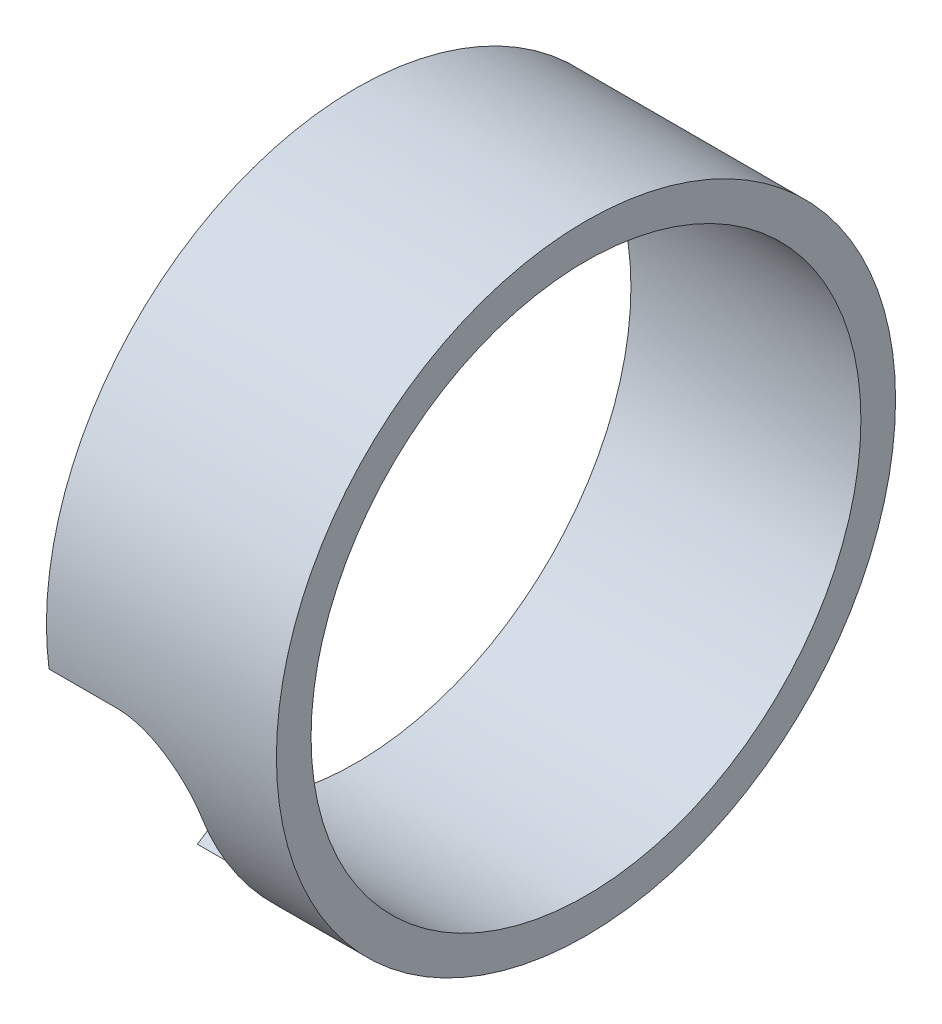
SolidWorks part; units mm, degrees
material "Nylon 6/10"
ref_plane "Front Plane" through (0, 0, 0) normal (0, 0, 1) x (1, 0, 0)
ref_plane "Top Plane" through (0, 0, 0) normal (0, 1, 0) x (1, 0, 0)
ref_plane "Right Plane" through (0, 0, 0) normal (1, 0, 0) x (0, 0, -1)
sketch "Sketch1" plane through (0, 0, 0) normal (0, 0, 1) x (1, 0, 0)
  line L0 (-25.4, 7.5) -> (-42.315, 7.5) construction
  line L1 (-39.013, 8.7312) -> (-32.527, 8.7312)
  line L2 (-39.013, 8.7312) -> (-39.013, 7.754)
  line L3 (-39.013, 7.754) -> (-32.527, 7.754)
  line L4 (-32.527, 8.7312) -> (-32.527, 7.754)
  line L5 (-39.14, -5.7508) -> (-39.14, 0.3233) construction
  line L6 (-32.4, 15.2446) -> (-32.4, -15.2446) construction
  line L7 (0, 0) -> (-47.1489, 0) construction
  dimension "D1" = 0.254
  dimension "D2" = 0.127
  dimension "D3" = 0.127
  dimension "D4" = 17.4625
revolve "Revolve1" add sketch "Sketch1" angle 360 about L7
ref_plane "Plane1" through (0, 0, 0) normal (0, -0.549, 0.8358) x (1, 0, 0)
sketch "Sketch3" plane through (0, 0, 0) normal (0, -0.549, 0.8358) x (1, 0, 0)
  line L0 (-39.013, 3.81) -> (-39.013, -3.81)
  line L1 (-39.013, 7.754) -> (-39.013, -7.754) construction
  line L2 (-39.013, -3.81) -> (-37.108, -3.81)
  line L3 (-35.203, -1.905) -> (-35.203, 1.905)
  line L4 (-37.108, 3.81) -> (-39.013, 3.81)
  line L5 (-39.013, 8.7313) -> (-39.013, -8.7312) construction
  line L6 (-39.013, 8.7313) -> (-39.013, -8.7312) construction
  line L7 (-35.203, 0) -> (-39.013, 0) construction
  arc A0 (-37.108, -3.81) -> (-35.203, -1.905) centre (-37.108, -1.905) ccw
  arc A1 (-35.203, 1.905) -> (-37.108, 3.81) centre (-37.108, 1.905) ccw
  dimension "D1" = 7.62
  dimension "D2" = 3.81
extrude "Cut-Extrude1" cut sketch "Sketch3" along normal up to next
